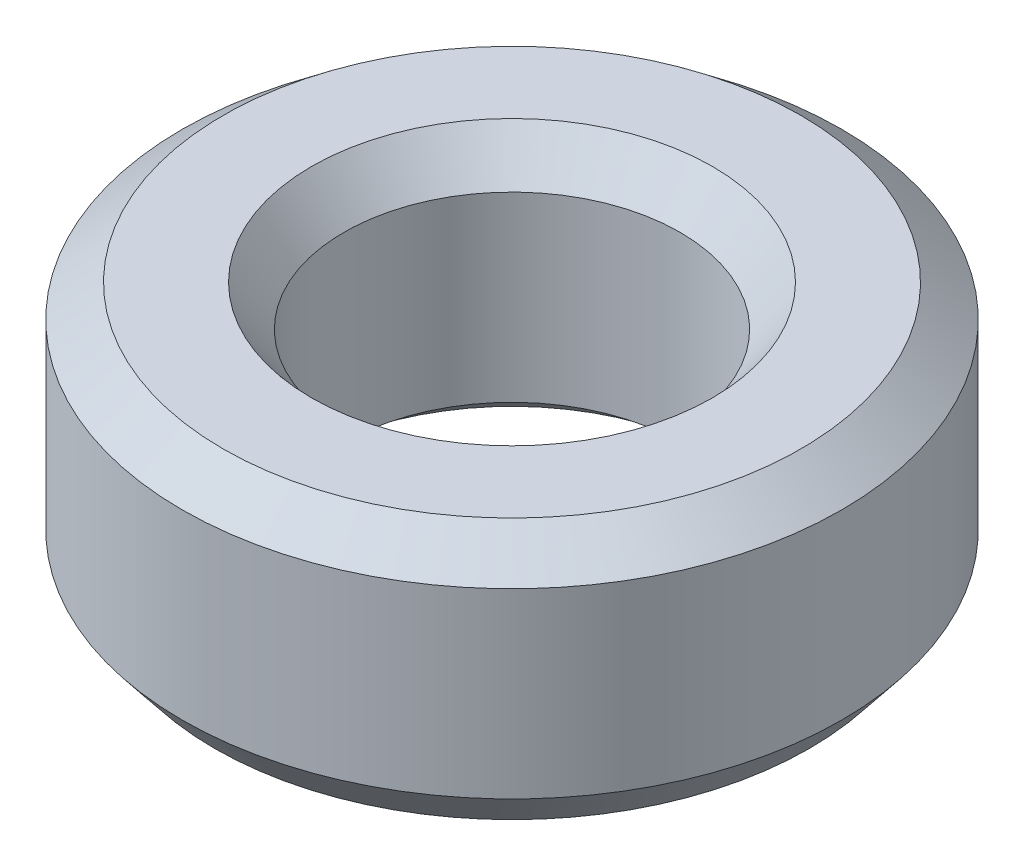
SolidWorks part; units mm, degrees
ref_plane "Front Plane" through (0, 0, 0) normal (0, 0, 1) x (1, 0, 0)
ref_plane "Top Plane" through (0, 0, 0) normal (0, 1, 0) x (1, 0, 0)
ref_plane "Right Plane" through (0, 0, 0) normal (1, 0, 0) x (0, 0, -1)
sketch "Sketch1" plane through (0, 0, 0) normal (0, 1, 0) x (1, 0, 0)
  circle A0 centre (0, 0) radius 35
  dimension "SLEEVE_OD" = 70
extrude "Boss-Extrude1" add sketch "Sketch1" along normal blind 27.0984
sketch "Sketch2" plane through (0, 0, 0) normal (0, 1, 0) x (1, 0, 0)
  circle A0 centre (0, 0) radius 17.8408
  dimension "BORE_D" = 35.6816
extrude "Cut-Extrude1" cut sketch "Sketch2" along normal through all
chamfer "Chamfer1" distance 3.4387 angle 51.569 4 edges at (0, 27.0984, 17.8408) (0, 0, 17.8408) (0, 0, 35) (0, 27.0984, 35) first distance on face at (0, 27.0984, 17.8408) first distance on face at (0, 0, 17.8408) first distance on face at (0, 27.0984, 35)
